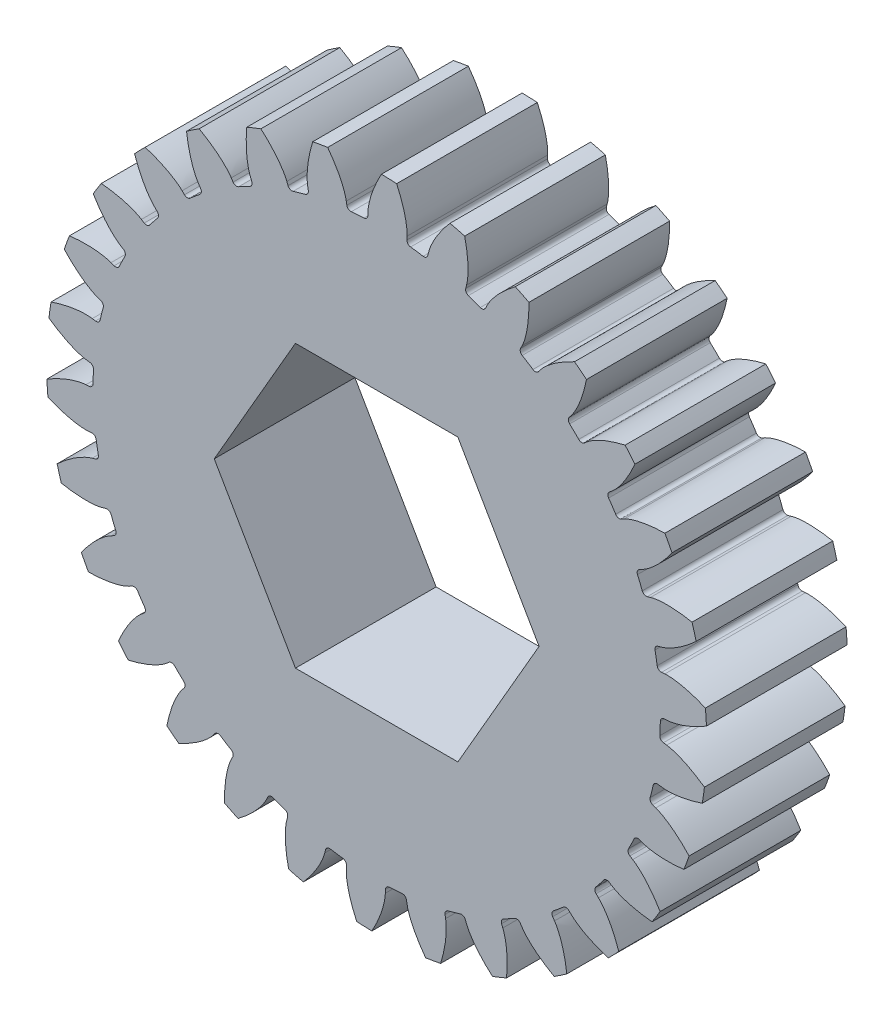
SolidWorks part; units mm, degrees
ref_plane "Front Plane" through (0, 0, 0) normal (0, 0, 1) x (1, 0, 0)
ref_plane "Top Plane" through (0, 0, 0) normal (0, 1, 0) x (1, 0, 0)
ref_plane "Right Plane" through (0, 0, 0) normal (1, 0, 0) x (0, 0, -1)
sketch "Sketch1" plane through (0, 0, 0) normal (0, 0, 1) x (1, 0, 0)
  line L0 (0, 0) -> (32.9254, 2.2181) construction
  circle A0 centre (0, 0) radius 30.25
  circle A1 centre (0, 0) radius 31.0099
  circle A2 centre (0, 0) radius 33 construction
  circle A3 centre (0, 0) radius 35.2
  arc A4 (32.9963, 0.4918) -> (32.7642, 3.9382) centre (0, 0) ccw
  spline S0 degree 4 poles (31.0099, 0) (31.0576, 0.0015) (31.153, 0.0074) (31.4195, 0.0389) (31.9214, 0.1374) (32.6755, 0.3542) (33.6783, 0.7504) (34.9156, 1.3757) (36.2888, 2.2432) (37.7039, 3.3305) (39.12, 4.6321) (40.4288, 6.041) (41.6327, 7.5402) (42.7883, 9.1941) (44.0802, 11.3326) (45.408, 14.0016) (46.6554, 17.2324) (47.6806, 20.9416) (48.3611, 24.7284) (48.7131, 28.5592) (48.7523, 32.4055) (48.5263, 35.7632) (48.1558, 38.6226) (47.7338, 40.9873) (47.3301, 42.8659) (46.8619, 44.7298) (46.3311, 46.5763) (45.7391, 48.4049) (45.1698, 49.9861) (44.6449, 51.3296) (44.2479, 52.2861) (43.9955, 52.8736) (43.7797, 53.3649) (43.5471, 53.8831) (43.3516, 54.3091) (42.9718, 55.1168) (42.6734, 55.7225) (42.2994, 56.4706) (41.9583, 57.1239) (41.5823, 57.8307) (41.2167, 58.4926) (40.9242, 59.012) (40.7344, 59.3398) (40.6354, 59.5106) knots 0 0 0 0 0 0.002802 0.005604 0.015718 0.02996 0.048734 0.068727 0.096889 0.125051 0.153212 0.181374 0.209535 0.237696 0.271429 0.327752 0.384075 0.440398 0.496721 0.553044 0.609367 0.66569 0.693852 0.722013 0.750174 0.778336 0.806497 0.834659 0.86282 0.876901 0.890982 0.895509 0.900036 0.909091 0.920455 0.931818 0.943182 0.954545 0.965909 0.977273 0.988636 1 1 1 1 1 construction
  spline S1 degree 4 poles (31.0099, 0) (31.0576, 0.0015) (31.153, 0.0074) (31.4195, 0.0389) (31.9214, 0.1374) (32.6755, 0.3542) (33.6783, 0.7504) (34.9156, 1.3757) (36.2888, 2.2432) (37.7039, 3.3305) (39.12, 4.6321) (40.4288, 6.041) (41.6327, 7.5402) (42.7883, 9.1941) (44.0802, 11.3326) (45.408, 14.0016) (46.6554, 17.2324) (47.6806, 20.9416) (48.3611, 24.7284) (48.7131, 28.5592) (48.7523, 32.4055) (48.5263, 35.7632) (48.1558, 38.6226) (47.7338, 40.9873) (47.3301, 42.8659) (46.8619, 44.7298) (46.3311, 46.5763) (45.7391, 48.4049) (45.1698, 49.9861) (44.6449, 51.3296) (44.2479, 52.2861) (43.9955, 52.8736) (43.7797, 53.3649) (43.6368, 53.6833) (43.5481, 53.8788) (43.4897, 54.0065) knots 0 0 0 0 0 0.002802 0.005604 0.015718 0.02996 0.048734 0.068727 0.096889 0.125051 0.153212 0.181374 0.209535 0.237696 0.271429 0.327752 0.384075 0.440398 0.496721 0.553044 0.609367 0.66569 0.693852 0.722013 0.750174 0.778336 0.806497 0.834659 0.86282 0.876901 0.890982 0.895509 0.900036 0.909091 0.909091 0.909091 0.909091 0.909091
  dimension "D1" = 60.5
  dimension "D2" = 62.0197
  dimension "D3" = 66
  dimension "D4" = 70.4
  dimension "D5" = 3.4558
extrude "Boss-Extrude1" add sketch "Sketch1" along normal mid plane 15 contours A0
sketch "Sketch4" plane through (0, 0, 0) normal (0, 0, 1) x (1, 0, 0)
  line L0 (0, 0) -> (32.9254, 2.2181) construction
  line L1 (0, 0) -> (32.9254, 2.2181) construction
  line L2 (31.0099, 0) -> (30.25, -0.0512)
  line L3 (30.7297, 4.1592) -> (29.9698, 4.108)
  circle A0 centre (0, 0) radius 31.0099 construction
  circle A1 centre (0, 0) radius 30.25 construction
  circle A2 centre (0, 0) radius 31.0099
  circle A3 centre (0, 0) radius 30.25
extrude "Boss-Extrude2" add sketch "Sketch4" along normal mid plane 15 contours L1 A3 L2 A2 | A3 L1 A2 L3 region at (30.467, 3.0974, 0) region at (30.6071, 1.017, 0)
sketch "Sketch6" plane through (0, 0, 0) normal (0, 0, 1) x (1, 0, 0)
  line L0 (0, 0) -> (32.9254, 2.2181) construction
  line L1 (0, 0) -> (32.9254, 2.2181) construction
  circle A0 centre (0, 0) radius 31.0099 construction
  circle A1 centre (0, 0) radius 35.2 construction
  circle A2 centre (0, 0) radius 31.0099
  circle A3 centre (0, 0) radius 35.2
  spline S0 degree 4 poles (19.9798, -1999.4555) (22.4802, 64.9877) (25.7545, 1.2613) (28.8917, -0.4571) (31.9214, 0.1374) (32.6755, 0.3542) (33.6783, 0.7504) (34.9156, 1.3757) (36.2888, 2.2432) (37.7039, 3.3305) (39.12, 4.6321) (40.4288, 6.041) (41.6327, 7.5402) (42.7883, 9.1941) (44.0802, 11.3326) (45.408, 14.0016) (46.6554, 17.2324) (47.6806, 20.9416) (48.3611, 24.7284) (48.7131, 28.5592) (48.7523, 32.4055) (48.5263, 35.7632) (48.1558, 38.6226) (47.7338, 40.9873) (47.3301, 42.8659) (46.8619, 44.7298) (46.3311, 46.5763) (45.7391, 48.4049) (45.1698, 49.9861) (44.6449, 51.3296) (44.2479, 52.2861) (43.9955, 52.8736) (42.8987, 55.3706) (40.4315, 60.5154) (73.9045, -13.1683) (-789.1933, 1871.9335) knots -0.150874 -0.150874 -0.150874 -0.150874 -0.150874 0.002802 0.005604 0.015718 0.02996 0.048734 0.068727 0.096889 0.125051 0.153212 0.181374 0.209535 0.237696 0.271429 0.327752 0.384075 0.440398 0.496721 0.553044 0.609367 0.66569 0.693852 0.722013 0.750174 0.778336 0.806497 0.834659 0.86282 0.876901 0.890982 0.895509 0.900036 1.040494 1.040494 1.040494 1.040494 1.040494 only from (31.0099, 0) to (43.4897, 54.0065) construction
  spline S1 degree 4 poles (31.0099, 0) (31.0576, 0.0015) (31.153, 0.0074) (31.4195, 0.0389) (31.9214, 0.1374) (32.6755, 0.3542) (33.6783, 0.7504) (34.9156, 1.3757) (36.2888, 2.2432) (37.7039, 3.3305) (39.12, 4.6321) (40.4288, 6.041) (41.6327, 7.5402) (42.7883, 9.1941) (44.0802, 11.3326) (45.408, 14.0016) (46.6554, 17.2324) (47.6806, 20.9416) (48.3611, 24.7284) (48.7131, 28.5592) (48.7523, 32.4055) (48.5263, 35.7632) (48.1558, 38.6226) (47.7338, 40.9873) (47.3301, 42.8659) (46.8619, 44.7298) (46.3311, 46.5763) (45.7391, 48.4049) (45.1698, 49.9861) (44.6449, 51.3296) (44.2479, 52.2861) (43.9955, 52.8736) (43.7797, 53.3649) (43.6368, 53.6833) (43.5481, 53.8788) (43.4897, 54.0065) knots 0 0 0 0 0 0.002802 0.005604 0.015718 0.02996 0.048734 0.068727 0.096889 0.125051 0.153212 0.181374 0.209535 0.237696 0.271429 0.327752 0.384075 0.440398 0.496721 0.553044 0.609367 0.66569 0.693852 0.722013 0.750174 0.778336 0.806497 0.834659 0.86282 0.876901 0.890982 0.895509 0.900036 0.909091 0.909091 0.909091 0.909091 0.909091
  spline S2 degree 4 poles (30.7297, 4.1592) (30.7772, 4.1641) (30.8725, 4.171) (31.1408, 4.1755) (31.6514, 4.1452) (32.4278, 4.0315) (33.4747, 3.7734) (34.7846, 3.3197) (36.2618, 2.6443) (37.8099, 1.7566) (39.3878, 0.6566) (40.8738, -0.564) (42.2678, -1.8882) (43.6349, -3.3721) (45.2019, -5.318) (46.8757, -7.7848) (48.5451, -10.8191) (50.0585, -14.3573) (51.2408, -18.0186) (52.1035, -21.7676) (52.6582, -25.5738) (52.8845, -28.9315) (52.9009, -31.8148) (52.7999, -34.2147) (52.6518, -36.1305) (52.4378, -38.0403) (52.1595, -39.9414) (51.8181, -41.8329) (51.466, -43.4761) (51.126, -44.8779) (50.8609, -45.879) (50.6896, -46.495) (50.5416, -47.0108) (50.4427, -47.3455) (50.3811, -47.5512) (50.3403, -47.6855) knots 0 0 0 0 0 0.002802 0.005604 0.015718 0.02996 0.048734 0.068727 0.096889 0.125051 0.153212 0.181374 0.209535 0.237696 0.271429 0.327752 0.384075 0.440398 0.496721 0.553044 0.609367 0.66569 0.693852 0.722013 0.750174 0.778336 0.806497 0.834659 0.86282 0.876901 0.890982 0.895509 0.900036 0.909091 0.909091 0.909091 0.909091 0.909091
  point P10 (98.3926, 7.3625)
  point P11 (0, 0)
extrude "Boss-Extrude3" add sketch "Sketch6" along normal mid plane 15 contours S2 A2 S1 A3 region at (32.7317, 2.205, 0)
fillet "Fillet1" radius 0.44 2 edges at (30.25, -0.0512, 0) (29.9698, 4.108, 0)
pattern_circular "CirPattern1" count 30 over 360 about axis through (0, 0, 7.5) along (0, 0, -1) of "Boss-Extrude3", "Boss-Extrude2", "Fillet1" reverse direction yes
fillet "Fillet2" [suppressed] radius 0.44
pattern_circular "CirPattern2" [suppressed] count 30 over 360 reverse direction yes of bodies 120
sketch "Sketch7" plane through (0, 0, 7.5) normal (0, 0, 1) x (1, 0, 0)
  line L1 (8.6603, 15) -> (-8.6603, 15)
  line L2 (-8.6603, 15) -> (-17.3205, 0)
  line L3 (-17.3205, 0) -> (-8.6603, -15)
  line L4 (-8.6603, -15) -> (8.6603, -15)
  line L5 (8.6603, -15) -> (17.3205, 0)
  line L6 (17.3205, 0) -> (8.6603, 15)
  circle A0 centre (0, 0) radius 15 construction
  point P1 (-9.6177, 14.3387)
  dimension "D1" = 30
extrude "Cut-Extrude1" cut sketch "Sketch7" against normal through all
equation "\"m\" = 2.2'Модуль"
equation "\"z\"= 30'Число зубьев"
equation "\"b\" = 15mm'Ширина зубчатого венца"
equation "\"a\"= 20 * pi / 180'Угол профиля исходного контура"
equation "\"D\"= \"m\" * \"z\"'Диаметр делительной окружности"
equation "\"Db\"= \"D\" * cos ( \"a\" )'Диаметр начальной окружности"
equation "\"Da\"= \"D\" + \"m\" * 2'Диаметр вершин зубьев"
equation "\"Df\"= \"D\" - \"m\" * 2.5'Диаметр впадин зубьев"
equation "\"S\"= \"m\" * pi / 2'Толщина зуба по дуге"
equation "\"D1@Sketch1\"= \"Df\""
equation "\"D2@Sketch1\"=\"Db\""
equation "\"D3@Sketch1\"=\"D\""
equation "\"D4@Sketch1\"=\"Da\""
equation "\"D1@Boss-Extrude1\"=\"b\""
equation "\"D5@Sketch1\"=\"S\""
equation "\"D1@Boss-Extrude2\"=\"b\""
equation "\"D1@Boss-Extrude3\"=\"b\""
equation "\"D1@Fillet1\"=\"m\"*0.2"
equation "\"D1@CirPattern1\"=\"z\""
equation "\"Fillet1\"= IIF ( \"Df\" > \"Db\" , \"suppressed\" , \"unsuppressed\" )"
equation "\"CirPattern1\"= IIF ( \"Df\" > \"Db\" , \"suppressed\" , \"unsuppressed\" )"
equation "\"D1@Fillet2\"=\"m\"*0.2"
equation "\"D1@CirPattern2\"=\"z\""
equation "\"Fillet2\"= IIF ( \"Db\" > \"Df\" , \"suppressed\" , \"unsuppressed\" )"
equation "\"CirPattern2\"= IIF ( \"Db\" > \"Df\" , \"suppressed\" , \"unsuppressed\" )"
